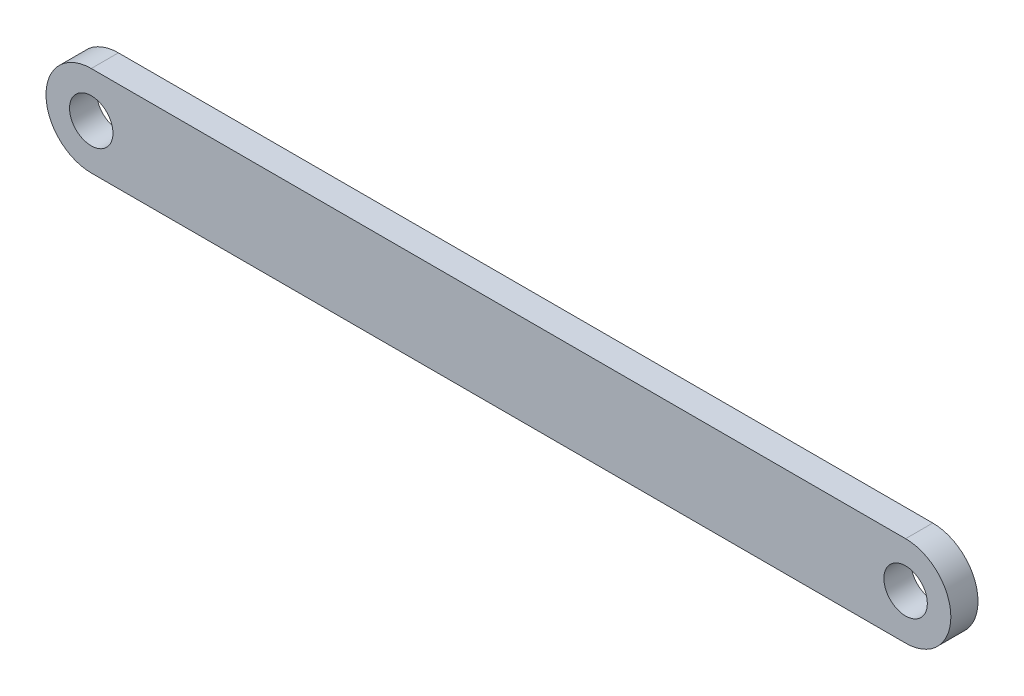
SolidWorks part; units mm, degrees
ref_plane "Front Plane" through (0, 0, 0) normal (0, 0, 1) x (1, 0, 0)
ref_plane "Top Plane" through (0, 0, 0) normal (0, 1, 0) x (1, 0, 0)
ref_plane "Right Plane" through (0, 0, 0) normal (1, 0, 0) x (0, 0, -1)
sketch "Sketch1" plane through (0, 0, 0) normal (0, 0, 1) x (1, 0, 0)
  line L1 (120.0787, 190.0323) -> (210.0787, 190.0323)
  line L3 (120.0787, 200.0323) -> (210.0787, 200.0323)
  arc A0 (120.0787, 200.0323) -> (120.0787, 190.0323) centre (120.0787, 195.0323) ccw
  arc A1 (210.0787, 200.0323) -> (210.0787, 190.0323) centre (210.0787, 195.0323) cw
  circle A2 centre (120.0787, 195.0323) radius 2.4
  circle A3 centre (210.0787, 195.0323) radius 2.4
  dimension "D3" = 4.8
  dimension "D4" = 4.8
  dimension "D1" = 90
  dimension "D2" = 10
extrude "Boss-Extrude1" add sketch "Sketch1" along normal blind 3
